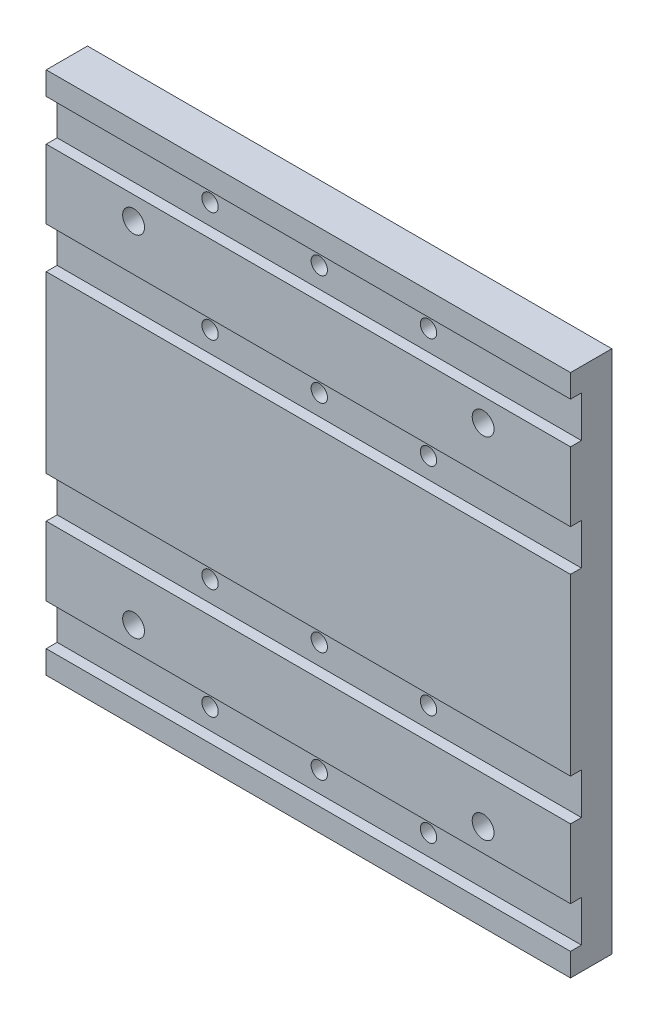
SolidWorks part; units mm, degrees
ref_plane "Front Plane" through (0, 0, 0) normal (0, 0, 1) x (1, 0, 0)
ref_plane "Top Plane" through (0, 0, 0) normal (0, 1, 0) x (1, 0, 0)
ref_plane "Right Plane" through (0, 0, 0) normal (1, 0, 0) x (0, 0, -1)
sketch "Sketch1" plane through (0, 0, 0) normal (0, 0, 1) x (1, 0, 0)
  line L1 (-76.2, 76.2) -> (76.2, 76.2)
  line L2 (-76.2, 76.2) -> (-76.2, -76.2)
  line L3 (-76.2, -76.2) -> (76.2, -76.2)
  line L4 (76.2, 76.2) -> (76.2, -76.2)
  line L5 (-76.2, 76.2) -> (76.2, -76.2) construction
  line L6 (-76.2, -76.2) -> (76.2, 76.2) construction
  circle A0 centre (-50.8, 50.8) radius 3.175
  circle A1 centre (-50.8, -50.8) radius 3.175
  circle A2 centre (50.8, 50.8) radius 3.175
  circle A3 centre (50.8, -50.8) radius 3.175
  point P0 (0, 0)
  point P14 (0, 0)
  dimension "D5" = 6.35
  dimension "D6" = 6.35
  dimension "D7" = 6.35
  dimension "D8" = 6.35
  dimension "D9" = 25.4
  dimension "D10" = 25.4
  dimension "D11" = 25.4
  dimension "D12" = 25.4
  dimension "D13" = 25.4
  dimension "D14" = 25.4
  dimension "D15" = 25.4
  dimension "D16" = 101.6
  dimension "D1" = 0
  dimension "D2" = 0
  dimension "D3" = 152.4
  dimension "D4" = 152.4
extrude "Boss-Extrude1" add sketch "Sketch1" along normal blind 12
sketch "Sketch2" plane through (0, 0, 12) normal (0, 0, 1) x (1, 0, 0)
  line L0 (76.2, -76.2) -> (76.2, 76.2) construction
  line L1 (-76.2, -25.4) -> (76.2, -25.4)
  line L2 (-76.2, -25.4) -> (-76.2, -37.4)
  line L3 (-76.2, -37.4) -> (76.2, -37.4)
  line L4 (76.2, -25.4) -> (76.2, -37.4)
  line L5 (-76.2, -25.4) -> (76.2, -37.4) construction
  line L6 (-76.2, -37.4) -> (76.2, -25.4) construction
  line L7 (-76.2, 37.4) -> (76.2, 37.4)
  line L8 (-76.2, 37.4) -> (-76.2, 25.4)
  line L9 (-76.2, 25.4) -> (76.2, 25.4)
  line L10 (76.2, 37.4) -> (76.2, 25.4)
  line L11 (-76.2, 37.4) -> (76.2, 25.4) construction
  line L12 (-76.2, 25.4) -> (76.2, 37.4) construction
  line L13 (-76.2, 69.5) -> (76.2, 69.5)
  line L14 (-76.2, 69.5) -> (-76.2, 57.5)
  line L15 (-76.2, 57.5) -> (76.2, 57.5)
  line L16 (76.2, 69.5) -> (76.2, 57.5)
  line L17 (-76.2, 69.5) -> (76.2, 57.5) construction
  line L18 (-76.2, 57.5) -> (76.2, 69.5) construction
  line L19 (-76.2, -57.5) -> (76.2, -57.5)
  line L20 (-76.2, -57.5) -> (-76.2, -69.5)
  line L21 (-76.2, -69.5) -> (76.2, -69.5)
  line L22 (76.2, -57.5) -> (76.2, -69.5)
  line L23 (-76.2, -57.5) -> (76.2, -69.5) construction
  line L24 (-76.2, -69.5) -> (76.2, -57.5) construction
  line L25 (-76.2, -76.2) -> (76.2, -76.2) construction
  line L26 (76.2, 76.2) -> (-76.2, 76.2) construction
  line L27 (-76.2, 76.2) -> (-76.2, -76.2) construction
  circle A0 centre (-31.75, 63.5) radius 2.3812
  circle A1 centre (0, 63.5) radius 2.3812
  circle A2 centre (0, -63.5) radius 2.3813
  circle A3 centre (0, -31.4) radius 2.3813
  circle A4 centre (0, 31.4) radius 2.3812
  circle A5 centre (31.75, 31.4) radius 2.3812
  circle A6 centre (-31.75, 31.4) radius 2.3812
  circle A7 centre (31.75, 63.5) radius 2.3812
  circle A8 centre (-31.75, -63.5) radius 2.3812
  circle A9 centre (31.75, -63.5) radius 2.3812
  circle A10 centre (-31.75, -31.4) radius 2.3812
  circle A11 centre (31.75, -31.4) radius 2.3812
  point P0 (0, -31.4)
  point P5 (0, 31.4)
  point P10 (0, 63.5)
  point P15 (0, -63.5)
  dimension "D18" = 4.7625
  dimension "D19" = 4.7625
  dimension "D20" = 4.7625
  dimension "D21" = 4.7625
  dimension "D22" = 4.7625
  dimension "D23" = 4.7625
  dimension "D24" = 4.7625
  dimension "D25" = 4.7625
  dimension "D28" = 4.7625
  dimension "D31" = 4.7625
  dimension "D17" = 31.75
  dimension "D32" = 31.75
  dimension "D35" = 31.75
  dimension "D37" = 0
  dimension "D40" = 4.7625
  dimension "D41" = 4.7625
  dimension "D45" = 6
  dimension "D46" = 6
  dimension "D1" = 152.4
  dimension "D2" = 12
  dimension "D3" = 0
  dimension "D4" = 152.4
  dimension "D5" = 12
  dimension "D6" = 12.7
  dimension "D7" = 12.7
  dimension "D8" = 0
  dimension "D9" = 152.4
  dimension "D10" = 0
  dimension "D11" = 12
  dimension "D12" = 50.8
  dimension "D13" = 152.4
  dimension "D14" = 12
  dimension "D15" = 50.8
  dimension "D16" = 0
  dimension "D26" = 0
  dimension "D27" = 0
  dimension "D29" = 0
  dimension "D30" = 0
  dimension "D33" = 0
  dimension "D34" = 31.75
  dimension "D36" = 0
  dimension "D38" = 31.75
  dimension "D39" = 31.75
  dimension "D42" = 31.75
  dimension "D43" = 31.75
  dimension "D44" = 6
extrude "Cut-Extrude1" cut sketch "Sketch2" against normal blind 3.175
sketch "Sketch3" plane through (0, 0, 12) normal (0, 0, 1) x (1, 0, 0)
  circle A0 centre (-31.75, 63.5) radius 2.3813
  circle A1 centre (0, 63.5) radius 2.3813
  circle A2 centre (31.75, 63.5) radius 2.3812
  circle A3 centre (-31.75, 31.4) radius 2.3812
  circle A4 centre (0, 31.4) radius 2.3813
  circle A5 centre (31.75, 31.4) radius 2.3813
  circle A6 centre (-31.75, -31.4) radius 2.3812
  circle A7 centre (0, -31.4) radius 2.3813
  circle A8 centre (31.75, -31.4) radius 2.3813
  circle A9 centre (-31.75, -63.5) radius 2.3812
  circle A10 centre (0, -63.5) radius 2.3813
  circle A11 centre (31.75, -63.5) radius 2.3812
extrude "Cut-Extrude2" cut sketch "Sketch3" against normal through all
sketch "Sketch5" plane through (0, 0, 0) normal (0, 0, -1) x (-1, 0, 0)
  circle A0 centre (31.75, -63.5) radius 3.9687
  circle A1 centre (0, -63.5) radius 3.9688
  circle A2 centre (-31.75, -63.5) radius 3.9688
  circle A3 centre (-31.75, -31.4) radius 3.9688
  circle A4 centre (0, -31.4) radius 3.9688
  circle A5 centre (31.75, -31.4) radius 3.9687
  circle A6 centre (31.75, 31.4) radius 3.9687
  circle A7 centre (0, 31.4) radius 3.9688
  circle A8 centre (-31.75, 31.4) radius 3.9688
  circle A9 centre (-31.75, 63.5) radius 3.9688
  circle A10 centre (0, 63.5) radius 3.9687
  circle A11 centre (31.75, 63.5) radius 3.9687
  dimension "D1" = 7.9375
  dimension "D2" = 7.9375
  dimension "D3" = 7.9375
  dimension "D4" = 7.9375
  dimension "D5" = 7.9375
  dimension "D6" = 7.9375
  dimension "D7" = 7.9375
  dimension "D8" = 7.9375
  dimension "D9" = 7.9375
  dimension "D10" = 7.9375
  dimension "D11" = 7.9375
  dimension "D12" = 7.9375
extrude "Cut-Extrude7" cut sketch "Sketch5" against normal blind 5.08
